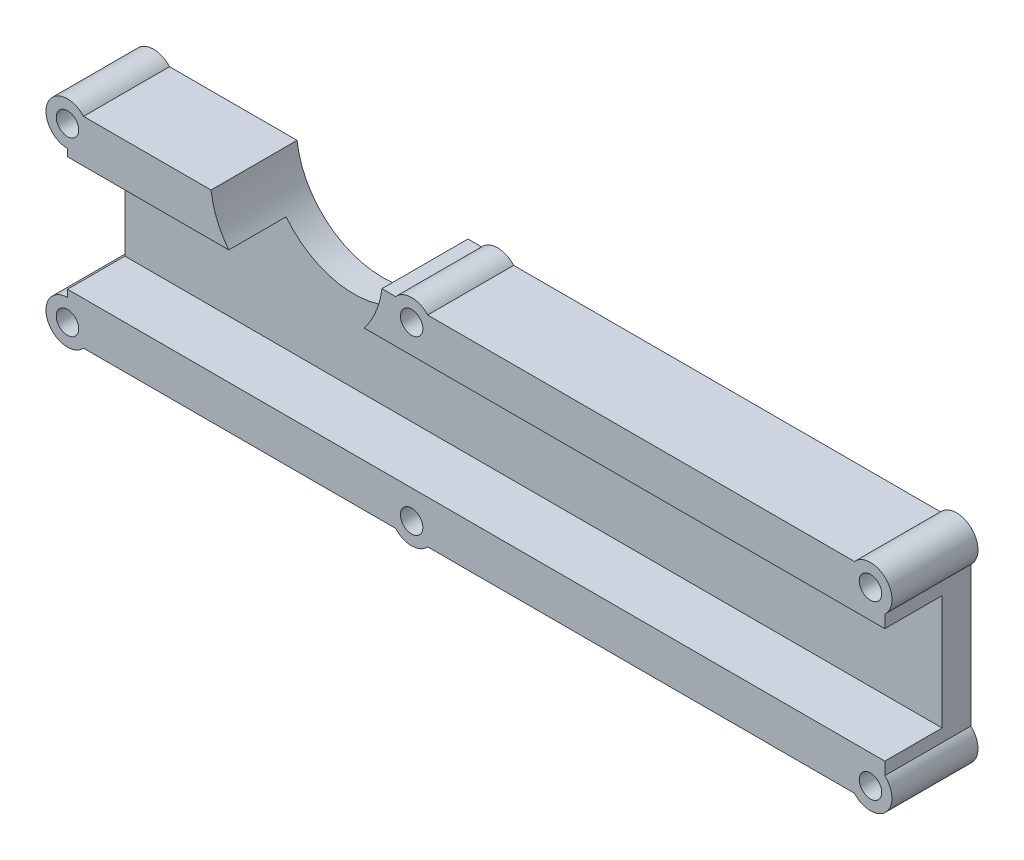
SolidWorks part; units mm, degrees
material "Nylon 101"
ref_plane "Front Plane" through (0, 0, 0) normal (0, 0, 1) x (1, 0, 0)
ref_plane "Top Plane" through (0, 0, 0) normal (0, 1, 0) x (1, 0, 0)
ref_plane "Right Plane" through (0, 0, 0) normal (1, 0, 0) x (0, 0, -1)
sketch "Sketch1" plane through (0, 0, 0) normal (0, 0, 1) x (1, 0, 0)
  line L0 (0, 38.1) -> (101.6, 38.1) construction
  line L1 (3.5498, -3.175) -> (98.0502, -3.175)
  line L3 (3.5498, 41.275) -> (98.0502, 41.275)
  line L4 (104.775, 3.5498) -> (104.775, 34.5502)
  line L5 (101.6, 0) -> (101.6, 38.1) construction
  line L6 (0, 0) -> (101.6, 0) construction
  line L8 (-3.175, 41.275) -> (104.775, 41.275) construction
  line L9 (-3.175, -3.175) -> (-3.175, 41.275) construction
  line L10 (-3.175, -3.175) -> (104.775, -3.175) construction
  line L11 (104.775, -3.175) -> (104.775, 41.275) construction
  line L12 (-3.5498, 41.275) -> (-6.5729, 41.275)
  line L13 (0, 0) -> (-76.2, 0) construction
  line L15 (0, 38.1) -> (-76.2, 38.1) construction
  line L17 (-76.2, 4.7625) -> (-76.2, 33.3375)
  line L18 (-72.6502, -3.175) -> (-3.5498, -3.175)
  line L19 (-44.4127, 41.275) -> (-72.6502, 41.275)
  line L20 (0, 0) -> (0, 38.1) construction
  circle A4 centre (0, 38.1) radius 2.4892
  circle A5 centre (0, 0) radius 2.4892
  circle A6 centre (101.6, 38.1) radius 2.4892
  circle A7 centre (101.6, 0) radius 2.4892
  arc A8 (3.5498, 41.275) -> (-3.5498, 41.275) centre (0, 38.1) ccw
  arc A9 (-3.5498, -3.175) -> (3.5498, -3.175) centre (0, 0) ccw
  circle A10 centre (101.6, 0) radius 4.7625
  circle A11 centre (101.6, 38.1) radius 4.7625
  circle A12 centre (-76.2, 38.1) radius 2.4892
  circle A14 centre (-76.2, 0) radius 2.4892
  arc A15 (-72.6502, 41.275) -> (-76.2, 33.3375) centre (-76.2, 38.1) ccw
  arc A16 (-76.2, 4.7625) -> (-72.6502, -3.175) centre (-76.2, 0) ccw
  arc A17 (-44.4127, 41.275) -> (-6.5729, 41.275) centre (-25.4928, 43.4975) ccw
  point P20 (-35.5701, 19.05)
  dimension "D3" = 4.9784
  dimension "D5" = 9.525
  dimension "D7" = 38.1
  dimension "D1" = 38.1
  dimension "D2" = 101.6
  dimension "D6" = 76.2
  dimension "D8" = 25.4928
  dimension "D9" = 5.3975
  dimension "D4" = 3.175
extrude "Boss-Extrude1" add sketch "Sketch1" along normal blind 19.05 contours L1 L4 L3 A7 A6 A5 A4 | A8 A4 | A9 A5 | A10 A7 | A11 A6 region at (15.12, 18.0645, 0) region at (98.3277, 3.2723, 0) region at (98.3277, 34.8277, 0)
sketch "Sketch2" plane through (-76.2, 0, 0) normal (-1, 0, 0) x (0, 0, 1)
  line L0 (0, 4.7625) -> (0, 33.3375) construction
  line L16 (0, 31.75) -> (0, 6.35)
  line L17 (0, 6.35) -> (12.7, 6.35)
  line L18 (12.7, 6.35) -> (12.7, 31.75)
  line L19 (12.7, 31.75) -> (0, 31.75)
  point P3 (0, 19.05)
  point P9 (0, 19.05)
  dimension "D1" = 12.7
  dimension "D2" = 25.4
extrude "Cut-Extrude1" cut sketch "Sketch2" against normal through all
mirror "Mirror1" about plane through (0, 0, 19.05) normal (0, 0, 1) of bodies 103
delete or keep bodies "Body-Delete/Keep 1" type delete bodies bodies 103
